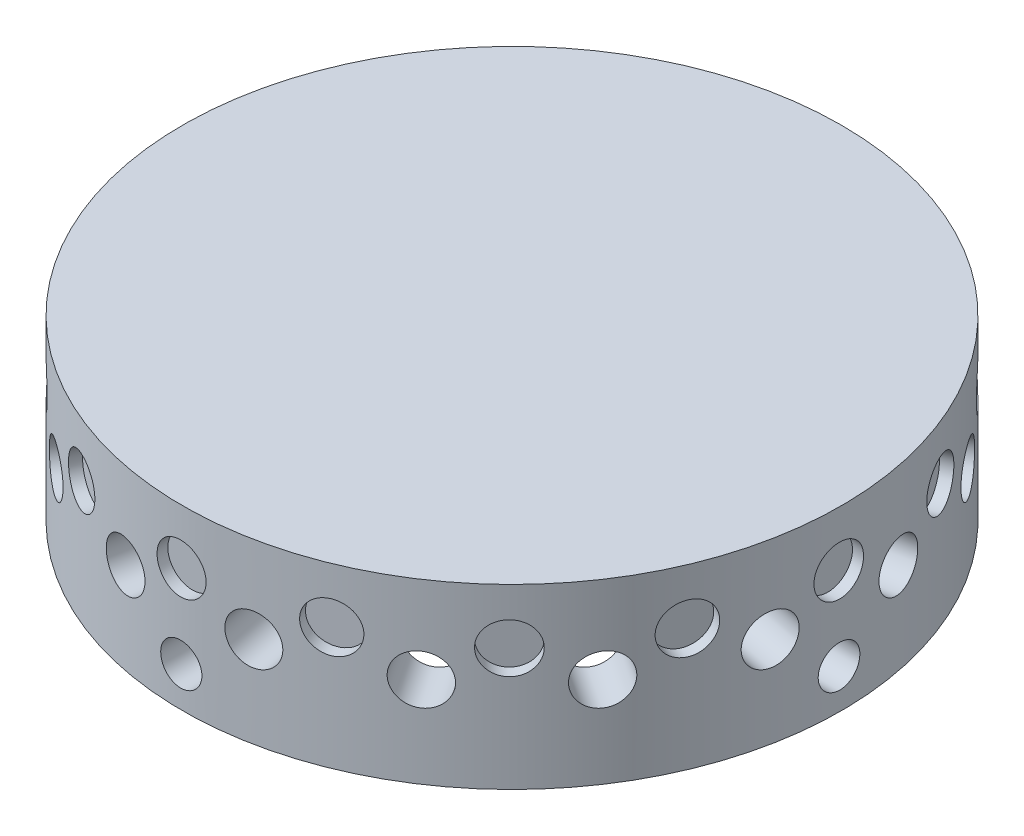
SolidWorks part; units mm, degrees
ref_plane "Płaszczyzna przednia" through (0, 0, 0) normal (0, 0, 1) x (1, 0, 0)
ref_plane "Płaszczyzna górna" through (0, 0, 0) normal (0, 1, 0) x (1, 0, 0)
ref_plane "Płaszczyzna prawa" through (0, 0, 0) normal (1, 0, 0) x (0, 0, -1)
sketch "Szkic1" plane through (0, 0, 0) normal (0, 0, 1) x (1, 0, 0)
  line L0 (0, -200.6294) -> (0, 200.6294) construction
  line L1 (0, 70.8485) -> (-83.5, 70.8485)
  line L2 (-83.5, 70.8485) -> (-83.5, 40.8485)
  line L4 (-83.5, 40.8485) -> (-83.5, 25.8485)
  line L5 (-83.5, 25.8485) -> (-70.5, 25.8485)
  line L6 (-70.5, 25.8485) -> (-70.5, 65.8485)
  line L7 (-70.5, 65.8485) -> (0, 65.8485)
  line L8 (0, 65.8485) -> (0, 70.8485)
  dimension "D1" = 70.5
  dimension "D2" = 40
  dimension "D3" = 5
  dimension "D5" = 13
revolve "Obrót1" add sketch "Szkic1" angle 360 about L0
ref_plane "Płaszczyzna1" through (83.5, 0, 0) normal (1, 0, 0) x (0, 0, -1)
sketch "Szkic2" plane through (83.5, 0, 0) normal (1, 0, 0) x (0, 0, -1)
  line L1 (83.5, 70.8485) -> (-83.5, 70.8485) construction
  circle A1 centre (-0.4671, 56.8485) radius 6.25
  dimension "D1" = 14
  dimension "D3" = 12.5
extrude "Wytnij-wyciągnięcie2" cut sketch "Szkic2" against normal blind 3
sketch "Szkic4" plane through (83.5, 0, 0) normal (1, 0, 0) x (0, 0, -1)
  line L1 (-83.5, 25.8485) -> (83.5, 25.8485) construction
  circle A0 centre (-0.4671, 35.8485) radius 5.25
  dimension "D1" = 10.5
  dimension "D2" = 10
extrude "Wytnij-wyciągnięcie4" cut sketch "Szkic4" against normal blind 30
pattern_circular "Szyk kołowy2" count 4 over 360 about axis through (0, -200.6294, 0) along (0, -1, 0) of "Wytnij-wyciągnięcie4" reverse direction yes
ref_plane "Płaszczyzna2" through (81.8956, 0, 16.29) normal (0.9808, 0, 0.1951) x (0, -1, 0)
sketch "Szkic8" plane through (81.8956, 0, 16.29) normal (0.9808, 0, 0.1951) x (0, -1, 0)
  line L0 (-70.8485, 83.5) -> (-70.8485, -83.5) construction
  circle A1 centre (-48.8485, 0) radius 6.25
  dimension "D1" = 22
  dimension "D2" = 12.5
extrude "Wytnij-wyciągnięcie5" cut sketch "Szkic8" against normal up to next
pattern_circular "Szyk kołowy3" count 16 over 360 about axis through (0, -200.6294, 0) along (0, -1, 0) of "Wytnij-wyciągnięcie2"
pattern_circular "Szyk kołowy4" count 16 over 360 about axis through (0, -200.6294, 0) along (0, -1, 0) of "Wytnij-wyciągnięcie5" reverse direction yes
